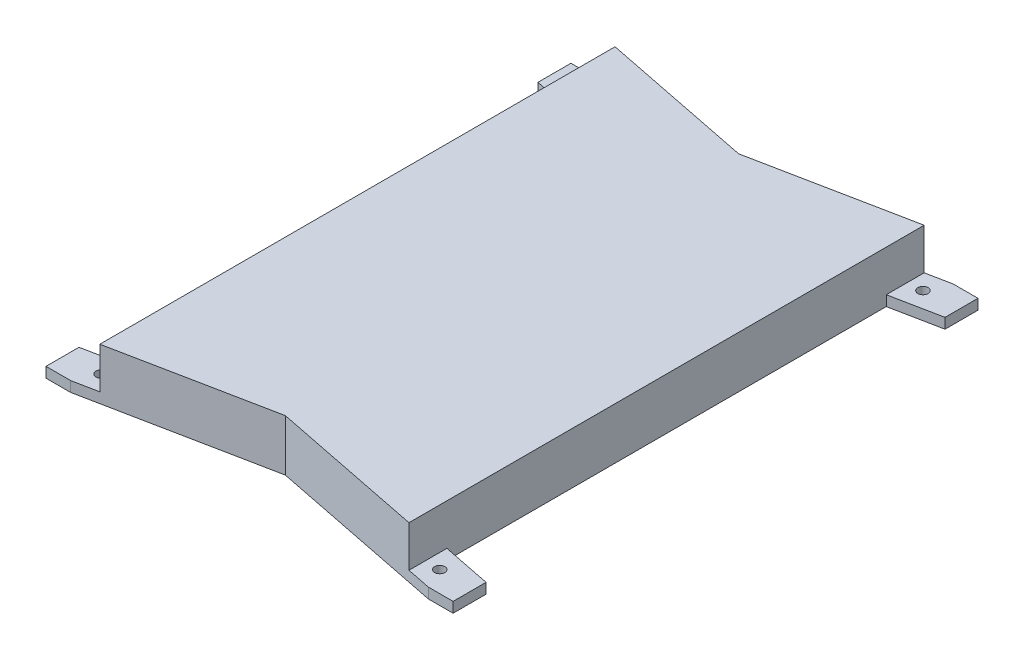
SolidWorks part; units mm, degrees
material "ABS"
ref_plane "Front Plane" through (0, 0, 0) normal (0, 0, 1) x (1, 0, 0)
ref_plane "Top Plane" through (0, 0, 0) normal (0, 1, 0) x (1, 0, 0)
ref_plane "Right Plane" through (0, 0, 0) normal (1, 0, 0) x (0, 0, -1)
ref_axis "X" through (-88.99, 0, 0) along (1, 0, 0)
ref_axis "Y" through (0, 55, 0) along (0, -1, 0)
ref_axis "Z" through (0, 0, -88.99) along (0, 0, 1)
sketch "Sketch1" plane through (0, 0, 0) normal (0, 1, 0) x (1, 0, 0)
  line L0 (-75, 106.6) -> (-75, -106.6)
  line L1 (-75, -125) -> (0, -110)
  line L2 (0, -110) -> (75, -125)
  line L3 (75, -106.6) -> (75, 106.6)
  line L4 (75, 125) -> (0, 110)
  line L5 (0, 110) -> (-75, 125)
  line L6 (0, 110) -> (0, -110) construction
  line L7 (-75, 0) -> (75, 0) construction
  line L8 (75, -125) -> (86.767, -127.3534)
  line L9 (86.767, -127.3534) -> (98.767, -127.3534)
  line L10 (98.767, -127.3534) -> (98.767, -111.3534)
  line L11 (98.767, -111.3534) -> (75, -106.6)
  line L12 (98.767, 111.3534) -> (75, 106.6)
  line L13 (98.767, 127.3534) -> (98.767, 111.3534)
  line L14 (86.767, 127.3534) -> (98.767, 127.3534)
  line L15 (75, 125) -> (86.767, 127.3534)
  line L16 (-98.767, -127.3534) -> (-98.767, -111.3534)
  line L17 (-86.767, -127.3534) -> (-98.767, -127.3534)
  line L18 (-75, -125) -> (-86.767, -127.3534)
  line L19 (-98.767, -111.3534) -> (-75, -106.6)
  line L20 (-98.767, 111.3534) -> (-75, 106.6)
  line L21 (-98.767, 127.3534) -> (-98.767, 111.3534)
  line L22 (-86.767, 127.3534) -> (-98.767, 127.3534)
  line L23 (-75, 125) -> (-86.767, 127.3534)
  line L24 (-75, 125) -> (-75, 106.6) construction
  line L25 (75, 125) -> (75, 106.6) construction
  line L26 (75, -106.6) -> (75, -125) construction
  line L27 (-75, -106.6) -> (-75, -125) construction
  dimension "D1" = 250
  dimension "D2" = 220
  dimension "D3" = 150
  dimension "D4" = 12
  dimension "D5" = 16
  dimension "D6" = 12
extrude "Boss-Extrude1" add sketch "Sketch1" along normal blind 5
sketch "Sketch3" plane through (0, 5, 0) normal (0, 1, 0) x (1, 0, 0)
  line L0 (-75, 106.6) -> (-75, 125) construction
  line L1 (0, 110) -> (-86.767, 127.3534) construction
  line L2 (75, 106.6) -> (75, 125) construction
  line L3 (86.767, 127.3534) -> (0, 110) construction
  line L4 (-75, -106.6) -> (-75, -125) construction
  line L5 (-86.767, -127.3534) -> (0, -110) construction
  line L6 (75, -106.6) -> (75, -125) construction
  line L7 (0, -110) -> (86.767, -127.3534) construction
  line L8 (-75, 106.6) -> (-75, -106.6) construction
  line L9 (75, -106.6) -> (75, 106.6) construction
  line L10 (75, 125) -> (0, 110)
  line L11 (0, 110) -> (-75, 125)
  line L12 (75, -106.6) -> (75, 106.6)
  line L13 (0, -110) -> (75, -125)
  line L14 (-75, 106.6) -> (-75, -106.6)
  line L15 (-75, -125) -> (0, -110)
  line L16 (-73, -122.5604) -> (0, -107.9604)
  line L17 (0, -107.9604) -> (73, -122.5604)
  line L18 (73, -106.6) -> (73, -122.5604)
  line L19 (73, -106.6) -> (73, 106.6)
  line L20 (73, 106.6) -> (73, 122.5604)
  line L21 (73, 122.5604) -> (0, 107.9604)
  line L22 (0, 107.9604) -> (-73, 122.5604)
  line L23 (-73, 106.6) -> (-73, 122.5604)
  line L24 (-73, 106.6) -> (-73, -106.6)
  line L25 (-73, -106.6) -> (-73, -122.5604)
  line L26 (75, 0) -> (-75, 0) construction
  line L27 (0, -110) -> (0, 110) construction
  line L28 (80.4076, -126.0815) -> (83.9461, -108.3892) construction
  line L29 (98.767, -111.3534) -> (75, -106.6) construction
  circle A0 centre (82.1768, -117.2354) radius 2.5
  circle A1 centre (-82.1768, -117.2354) radius 2.5
  circle A2 centre (-82.1768, 117.2354) radius 2.5
  circle A3 centre (82.1768, 117.2354) radius 2.5
  dimension "D2" = 5
  dimension "D3" = 82
  dimension "D1" = 2
extrude "Cut-Extrude1" cut sketch "Sketch3" against normal through all contours L24 L25 L16 L17 L18 L19 L20 L21 L22 L23 | A1 | A0 | A2 | A3 region at (0, 5, 0) region at (82.1768, 5, 117.2354) region at (-82.1768, 5, 117.2354) region at (-82.1768, 5, -117.2354) region at (82.1768, 5, -117.2354)
sketch "Sketch4" plane through (0, 5, 0) normal (0, 1, 0) x (1, 0, 0)
  line L0 (0, -107.9604) -> (73, -122.5604) construction
  line L1 (-73, -122.5604) -> (0, -107.9604) construction
  line L2 (73, 122.5604) -> (73, -122.5604) construction
  line L3 (73, 122.5604) -> (0, 107.9604) construction
  line L4 (0, 107.9604) -> (-73, 122.5604) construction
  line L5 (-73, 122.5604) -> (-73, -122.5604) construction
  line L6 (0, -107.9604) -> (73, -122.5604)
  line L7 (-73, -122.5604) -> (0, -107.9604)
  line L8 (73, 122.5604) -> (73, -122.5604)
  line L9 (73, 122.5604) -> (0, 107.9604)
  line L10 (0, 107.9604) -> (-73, 122.5604)
  line L11 (-73, 122.5604) -> (-73, -122.5604)
  line L12 (-75, 125) -> (-75, -125)
  line L13 (-75, -125) -> (0, -110)
  line L14 (0, -110) -> (75, -125)
  line L15 (75, 125) -> (75, -125)
  line L16 (75, 125) -> (0, 110)
  line L17 (0, 110) -> (-75, 125)
  dimension "D1" = 2
extrude "Boss-Extrude2" add sketch "Sketch4" along normal blind 20
sketch "Sketch5" plane through (0, 25, 0) normal (0, 1, 0) x (1, 0, 0)
  line L0 (75, 125) -> (0, 110) construction
  line L1 (0, 110) -> (-75, 125) construction
  line L2 (-75, 125) -> (-75, -125) construction
  line L3 (-75, -125) -> (0, -110) construction
  line L4 (0, -110) -> (75, -125) construction
  line L5 (75, -125) -> (75, 125) construction
  line L6 (75, 125) -> (0, 110)
  line L7 (0, 110) -> (-75, 125)
  line L8 (-75, 125) -> (-75, -125)
  line L9 (-75, -125) -> (0, -110)
  line L10 (0, -110) -> (75, -125)
  line L11 (75, -125) -> (75, 125)
extrude "Boss-Extrude3" add sketch "Sketch5" against normal blind 5
sketch "Sketch6" plane through (21.1538, 0, -105.7692) normal (0.1961, 0, -0.9806) x (-0.9806, 0, -0.1961)
  line L0 (31.5728, 2) -> (36.0728, 2)
  line L1 (31.5728, 10.5) -> (36.0728, 10.5)
  line L2 (21.5728, 0) -> (110.0581, 0) construction
  line L3 (21.5728, 25) -> (21.5728, 0) construction
  arc A1 (36.0728, 2) -> (36.0728, 10.5) centre (36.0728, 6.25) ccw
  arc A2 (31.5728, 2) -> (31.5728, 10.5) centre (31.5728, 6.25) cw
  point P6 (40.3467, 10.7021)
  point P11 (39.5728, 8.5)
  point P12 (27.3228, 6.25)
  point P13 (40.3228, 6.25)
  dimension "D1" = 13
  dimension "D2" = 8.5
  dimension "D3" = 2
  dimension "D4" = 10
extrude "Cut-Extrude2" cut sketch "Sketch6" against normal up to surface (2 mm away) up to face at (-36.5, 10, -115.2604)
